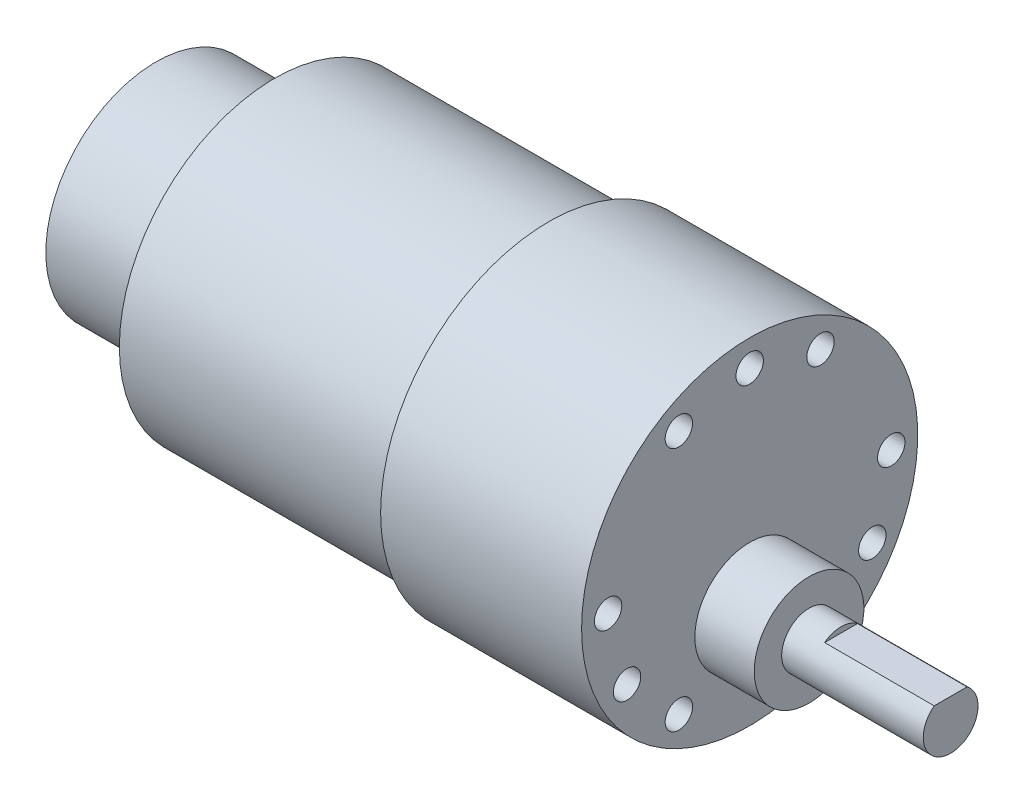
SolidWorks part; units mm, degrees
ref_plane "Plan de face" through (0, 0, 0) normal (0, 0, 1) x (1, 0, 0)
ref_plane "Plan de dessus" through (0, 0, 0) normal (0, 1, 0) x (1, 0, 0)
ref_plane "Plan de droite" through (0, 0, 0) normal (1, 0, 0) x (0, 0, -1)
sketch "Esquisse1" plane through (0, 0, 0) normal (0, 0, 1) x (1, 0, 0)
  line L0 (-59.1178, 0) -> (100.9551, 0) construction
  line L1 (-30, 0) -> (-30, 17)
  line L2 (-30, 17) -> (0, 17)
  line L3 (0, 17) -> (0, 18.4)
  line L4 (0, 18.4) -> (22, 18.4)
  line L5 (22, 18.4) -> (22, 0)
  line L10 (22, 0) -> (-30, 0)
  dimension "D1" = 17
  dimension "D2" = 18.4
  dimension "D3" = 30
  dimension "D4" = 22
revolve "Révolution1" add sketch "Esquisse1" angle 360 about L0
sketch "Esquisse3" plane through (0, 0, 0) normal (0, 0, 1) x (1, 0, 0)
  line L0 (8.4107, -7) -> (59.4134, -7) construction
  line L3 (22, -1) -> (28.5, -1)
  line L4 (28.5, -1) -> (28.5, -4)
  line L5 (28.5, -4) -> (44, -4)
  line L6 (44, -4) -> (44, -7)
  line L7 (44, -7) -> (22, -7)
  line L8 (22, -7) -> (22, -1)
  line L9 (22, -18.4) -> (22, 18.4) construction
  line L10 (31.7212, 0) -> (-32.2671, 0) construction
  dimension "D1" = 0
  dimension "D2" = 6.5
  dimension "D3" = 15.5
  dimension "D4" = 6
  dimension "D5" = 3
  dimension "D6" = 7
revolve "Révolution2" add sketch "Esquisse3" angle 360 about L0
sketch "Esquisse4" plane through (0, 0, 0) normal (0, 0, 1) x (1, 0, 0)
  line L0 (8.4107, -7) -> (59.4134, -7) construction
  line L1 (32, 6.8702) -> (50.6568, 6.8702)
  line L2 (32, 6.8702) -> (32, -4.6)
  line L3 (32, -4.6) -> (50.6568, -4.6)
  line L4 (50.6568, 6.8702) -> (50.6568, -4.6)
  line L5 (28.5, -1) -> (28.5, -4) construction
  dimension "D1" = 2.4
  dimension "D2" = 3.5
extrude "Enlèv. mat.-Extru.1" cut sketch "Esquisse4" against normal blind 10 and the other way blind 10
sketch "Esquisse5" plane through (-30, 0, 0) normal (-1, 0, 0) x (0, 0, 1)
  circle A0 centre (0, 0) radius 12.05
  circle A1 centre (0, 0) radius 11.9
  dimension "D1" = 24.1
extrude "Boss.-Extru.1" add sketch "Esquisse5" along normal blind 13
sketch "Esquisse6" plane through (22, 0, 0) normal (1, 0, 0) x (0, 0, -1)
  line L0 (0, 0) -> (-7.75, 13.4234) construction
  line L1 (0, 15.5) -> (0, 0) construction
  line L2 (0, 0) -> (7.75, 13.4234) construction
  circle A0 centre (0, 15.5) radius 1.5
  circle A1 centre (0, 0) radius 15.5 construction
  circle A2 centre (7.75, 13.4234) radius 1.5
  circle A3 centre (-7.75, 13.4234) radius 1.5
  dimension "D1" = 3
  dimension "D5" = 3
  dimension "D6" = 3
  dimension "D2" = 15.5
  dimension "D3" = 30
  dimension "D4" = 30
extrude "Enlèv. mat.-Extru.2" cut sketch "Esquisse6" against normal blind 5
pattern_circular "Répétition circulaire1" count 3 over 360 about axis through (22, 0, 0) along (-1, 0, 0) of "Enlèv. mat.-Extru.2"
